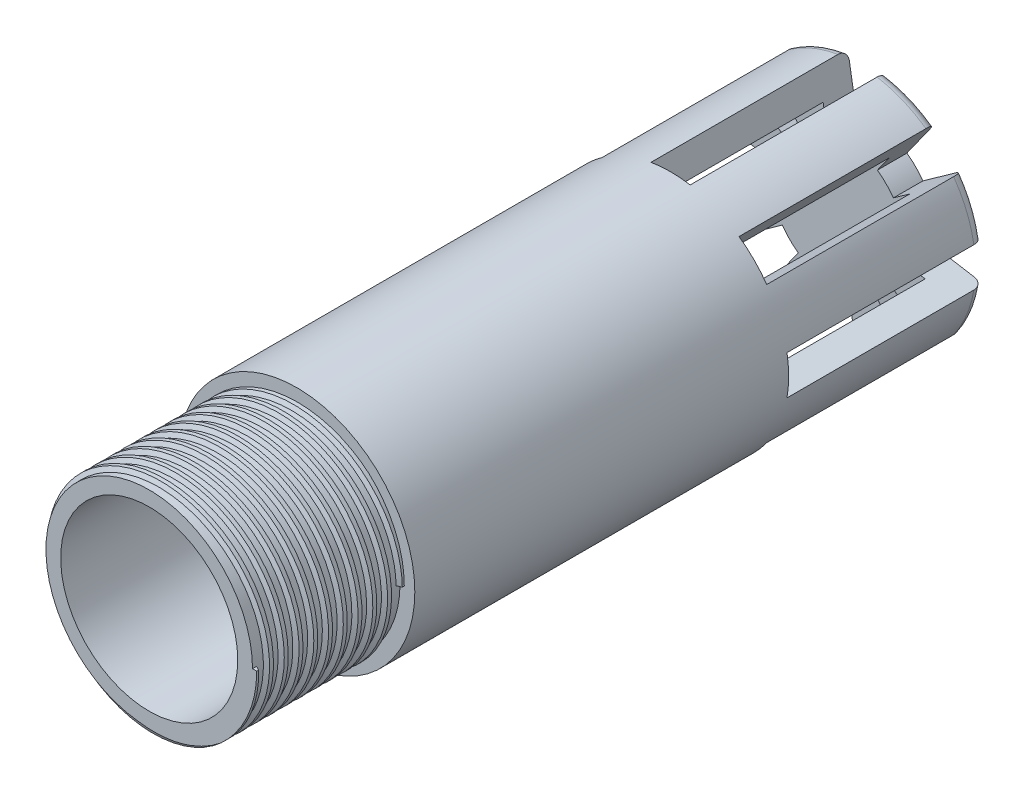
SolidWorks part; units mm, degrees
ref_plane "Front Plane" through (0, 0, 0) normal (0, 0, 1) x (1, 0, 0)
ref_plane "Top Plane" through (0, 0, 0) normal (0, 1, 0) x (1, 0, 0)
ref_plane "Right Plane" through (0, 0, 0) normal (1, 0, 0) x (0, 0, -1)
sketch "Sketch1" plane through (0, 0, 0) normal (0, 0, 1) x (1, 0, 0)
  circle A0 centre (0, 0) radius 9
  circle A1 centre (0, 0) radius 12
  dimension "D1" = 18
  dimension "D2" = 24
extrude "Boss-Extrude1" add sketch "Sketch1" along normal blind 70
sketch "Sketch2" plane through (0, 0, 0) normal (0, 0, -1) x (-1, 0, 0)
  circle A0 centre (0, 0) radius 12
extrude "Boss-Extrude2" add sketch "Sketch2" along normal blind 3
sketch "Sketch3" plane through (0, 0, 70) normal (0, 0, 1) x (1, 0, 0)
  circle A1 centre (0, 0) radius 10.5
  circle A2 centre (0, 0) radius 12
  dimension "D1" = 21
extrude "Cut-Extrude1" cut sketch "Sketch3" against normal blind 15
sketch "Sketch8" plane through (0, 0, -3) normal (0, 0, -1) x (-1, 0, 0)
  line L0 (0, 20.7908) -> (0, -22.2227) construction
  line L1 (-23.7373, 0) -> (33.1551, 0) construction
  line L2 (-1.1515, 6.8404) -> (-1.9921, 11.8335)
  line L3 (1.1515, 6.8404) -> (1.9921, 11.8335)
  line L4 (0, 0) -> (9.8254, 9.8254) construction
  line L5 (0, 0) -> (5.6491, 13.6382) construction
  line L6 (6.8404, 1.1515) -> (11.8335, 1.9921)
  line L7 (6.8404, -1.1515) -> (11.8335, -1.9921)
  line L8 (4.0226, 5.6512) -> (6.9589, 9.7762)
  line L9 (5.6512, 4.0226) -> (9.7762, 6.9589)
  line L10 (-6.8404, -1.1515) -> (-11.8335, -1.9921)
  line L11 (-6.8404, 1.1515) -> (-11.8335, 1.9921)
  line L12 (1.1515, -6.8404) -> (1.9921, -11.8335)
  line L13 (-1.1515, -6.8404) -> (-1.9921, -11.8335)
  line L14 (5.6512, -4.0226) -> (9.7762, -6.9589)
  line L15 (4.0226, -5.6512) -> (6.9589, -9.7762)
  line L16 (-4.0226, -5.6512) -> (-6.9589, -9.7762)
  line L17 (-5.6512, -4.0226) -> (-9.7762, -6.9589)
  line L18 (-5.6512, 4.0226) -> (-9.7762, 6.9589)
  line L19 (-4.0226, 5.6512) -> (-6.9589, 9.7762)
  arc A0 (1.1515, 6.8404) -> (-1.1515, 6.8404) centre (0, 0) ccw
  arc A1 (1.9921, 11.8335) -> (-1.9921, 11.8335) centre (0, 0) ccw
  arc A2 (11.8335, 1.9921) -> (11.8335, -1.9921) centre (0, 0) cw
  arc A3 (6.8404, 1.1515) -> (6.8404, -1.1515) centre (0, 0) cw
  arc A4 (6.9589, 9.7762) -> (9.7762, 6.9589) centre (0, 0) cw
  arc A5 (4.0226, 5.6512) -> (5.6512, 4.0226) centre (0, 0) cw
  arc A6 (-6.8404, 1.1515) -> (-6.8404, -1.1515) centre (0, 0) ccw
  arc A7 (-11.8335, 1.9921) -> (-11.8335, -1.9921) centre (0, 0) ccw
  arc A8 (1.9921, -11.8335) -> (-1.9921, -11.8335) centre (0, 0) cw
  arc A9 (1.1515, -6.8404) -> (-1.1515, -6.8404) centre (0, 0) cw
  arc A10 (4.0226, -5.6512) -> (5.6512, -4.0226) centre (0, 0) ccw
  arc A11 (6.9589, -9.7762) -> (9.7762, -6.9589) centre (0, 0) ccw
  arc A12 (-6.9589, -9.7762) -> (-9.7762, -6.9589) centre (0, 0) cw
  arc A13 (-4.0226, -5.6512) -> (-5.6512, -4.0226) centre (0, 0) cw
  arc A14 (-4.0226, 5.6512) -> (-5.6512, 4.0226) centre (0, 0) ccw
  arc A15 (-6.9589, 9.7762) -> (-9.7762, 6.9589) centre (0, 0) ccw
  dimension "D1" = 45
  dimension "D2" = 22.5
extrude "Cut-Extrude3" cut sketch "Sketch8" against normal blind 20
sketch "Sketch9" plane through (0, 0, -3) normal (0, 0, -1) x (-1, 0, 0)
  circle A0 centre (0, 0) radius 4.9159
extrude "Cut-Extrude4" cut sketch "Sketch9" against normal blind 2
sketch "Sketch10" plane through (0, 0, 70) normal (0, 0, 1) x (1, 0, 0)
  circle A0 centre (0, 0) radius 10.5
curve "Helix/Spiral1" pitch 1.5 height 15 radius 10.5 centre (0, 0, 70) axis (0, 0, -1) start towards (1, 0, 0)
sketch "Sketch11" plane through (0, 0, 0) normal (0, 1, 0) x (1, 0, 0)
  line L0 (-10.5, -58.75) -> (-10.9289, -58.75) construction
  line L1 (-10.5, -55) -> (-10.5, -70) construction
  line L2 (-10.9289, -58.55) -> (-10.9289, -58.95)
  line L3 (-10.9289, -58.95) -> (-10.5, -59.15)
  line L4 (-10.5, -59.15) -> (-10.5, -58.35)
  line L5 (-10.9289, -58.55) -> (-10.5, -58.35)
  spline S0 degree 3 poles (10.5, -70) (10.5, -69.969) (9.9533, -69.9062) (7.6179, -69.8125) (4.1228, -69.7187) (0, -69.625) (-4.1228, -69.5312) (-7.6179, -69.4375) (-9.9533, -69.3437) (-10.7734, -69.25) (-9.9533, -69.1562) (-7.6179, -69.0625) (-2.9577, -68.9375) (2.9577, -68.8125) (7.6179, -68.6875) (9.9533, -68.5937) (10.7734, -68.5) (9.9533, -68.4062) (7.6179, -68.3125) (2.9577, -68.1875) (-2.9577, -68.0625) (-7.6179, -67.9375) (-9.9533, -67.8438) (-10.7734, -67.75) (-9.9533, -67.6562) (-7.6179, -67.5625) (-2.9577, -67.4375) (2.9577, -67.3125) (7.6179, -67.1875) (9.9533, -67.0938) (10.7734, -67) (9.9533, -66.9062) (7.6179, -66.8125) (2.9577, -66.6875) (-2.9577, -66.5625) (-7.6179, -66.4375) (-9.9533, -66.3438) (-10.7734, -66.25) (-9.9533, -66.1562) (-7.6179, -66.0625) (-2.9577, -65.9375) (2.9577, -65.8125) (7.6179, -65.6875) (9.9533, -65.5938) (10.7734, -65.5) (9.9533, -65.4062) (7.6179, -65.3125) (2.9577, -65.1875) (-2.9577, -65.0625) (-7.6179, -64.9375) (-9.9533, -64.8438) (-10.7734, -64.75) (-9.9533, -64.6562) (-7.6179, -64.5625) (-2.9577, -64.4375) (2.9577, -64.3125) (7.6179, -64.1875) (9.9533, -64.0938) (10.7734, -64) (9.9533, -63.9062) (7.6179, -63.8125) (2.9577, -63.6875) (-2.9577, -63.5625) (-7.6179, -63.4375) (-9.9533, -63.3438) (-10.7734, -63.25) (-9.9533, -63.1563) (-7.6179, -63.0625) (-2.9577, -62.9375) (2.9577, -62.8125) (7.6179, -62.6875) (9.9533, -62.5937) (10.7734, -62.5) (9.9533, -62.4062) (7.6179, -62.3125) (2.9577, -62.1875) (-2.9577, -62.0625) (-7.6179, -61.9375) (-9.9533, -61.8438) (-10.7734, -61.75) (-9.9533, -61.6562) (-7.6179, -61.5625) (-2.9577, -61.4375) (2.9577, -61.3125) (7.6179, -61.1875) (9.9533, -61.0938) (10.7734, -61) (9.9533, -60.9063) (7.6179, -60.8125) (2.9577, -60.6875) (-2.9577, -60.5625) (-7.6179, -60.4375) (-9.9533, -60.3438) (-10.7734, -60.25) (-9.9533, -60.1563) (-7.6179, -60.0625) (-2.9577, -59.9375) (2.9577, -59.8125) (7.6179, -59.6875) (9.9533, -59.5938) (10.7734, -59.5) (9.9533, -59.4063) (7.6179, -59.3125) (2.9577, -59.1875) (-2.9577, -59.0625) (-7.6179, -58.9375) (-9.9533, -58.8438) (-10.7734, -58.75) (-9.9533, -58.6562) (-7.6179, -58.5625) (-2.9577, -58.4375) (2.9577, -58.3125) (7.6179, -58.1875) (9.9533, -58.0937) (10.7734, -58) (9.9533, -57.9062) (7.6179, -57.8125) (2.9577, -57.6875) (-2.9577, -57.5625) (-7.6179, -57.4375) (-9.9533, -57.3438) (-10.7734, -57.25) (-9.9533, -57.1563) (-7.6179, -57.0625) (-2.9577, -56.9375) (2.9577, -56.8125) (7.6179, -56.6875) (9.9533, -56.5938) (10.7734, -56.5) (9.9533, -56.4063) (7.6179, -56.3125) (2.9577, -56.1875) (-2.9577, -56.0625) (-7.6179, -55.9375) (-9.9533, -55.8438) (-10.7734, -55.75) (-9.9533, -55.6563) (-7.6179, -55.5625) (-4.1228, -55.4688) (0, -55.375) (4.1228, -55.2813) (7.6179, -55.1875) (9.9533, -55.0938) (10.5, -55.031) (10.5, -55) knots 0 0 0 0 0.00625 0.0125 0.01875 0.025 0.03125 0.0375 0.04375 0.05 0.05625 0.0625 0.06875 0.08125 0.0875 0.09375 0.1 0.10625 0.1125 0.11875 0.13125 0.1375 0.14375 0.15 0.15625 0.1625 0.16875 0.18125 0.1875 0.19375 0.2 0.20625 0.2125 0.21875 0.23125 0.2375 0.24375 0.25 0.25625 0.2625 0.26875 0.28125 0.2875 0.29375 0.3 0.30625 0.3125 0.31875 0.33125 0.3375 0.34375 0.35 0.35625 0.3625 0.36875 0.38125 0.3875 0.39375 0.4 0.40625 0.4125 0.41875 0.43125 0.4375 0.44375 0.45 0.45625 0.4625 0.46875 0.48125 0.4875 0.49375 0.5 0.50625 0.5125 0.51875 0.53125 0.5375 0.54375 0.55 0.55625 0.5625 0.56875 0.58125 0.5875 0.59375 0.6 0.60625 0.6125 0.61875 0.63125 0.6375 0.64375 0.65 0.65625 0.6625 0.66875 0.68125 0.6875 0.69375 0.7 0.70625 0.7125 0.71875 0.73125 0.7375 0.74375 0.75 0.75625 0.7625 0.76875 0.78125 0.7875 0.79375 0.8 0.80625 0.8125 0.81875 0.83125 0.8375 0.84375 0.85 0.85625 0.8625 0.86875 0.88125 0.8875 0.89375 0.9 0.90625 0.9125 0.91875 0.93125 0.9375 0.94375 0.95 0.95625 0.9625 0.96875 0.975 0.98125 0.9875 0.99375 1 1 1 1 construction
  dimension "D1" = 0.2
  dimension "D2" = 0.4
  dimension "D3" = 65
sweep "Sweep1" add profiles "Sketch11" path "Helix/Spiral1"
sketch "Sketch12" plane through (0, 0, 70) normal (0, 0, 1) x (1, 0, 0)
  circle A0 centre (0, 0) radius 11.9769
extrude "Cut-Extrude5" cut sketch "Sketch12" along normal blind 1
fillet "Fillet1" radius 1 8 edges at (-11.0866, -4.5922, -3) (-4.5922, -11.0866, -3) (4.5922, -11.0866, -3) (11.0866, -4.5922, -3) (11.0866, 4.5922, -3) (4.5922, 11.0866, -3) (-4.5922, 11.0866, -3) (-11.0866, 4.5922, -3)
